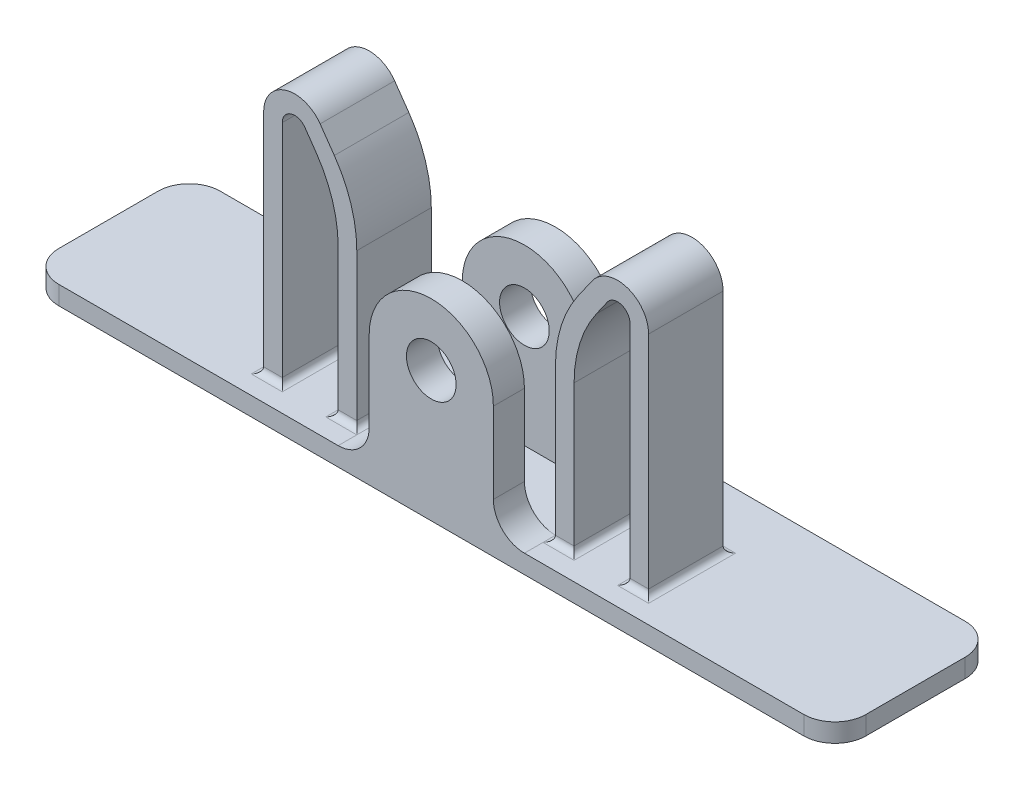
SolidWorks part; units mm, degrees
ref_plane "Front Plane" through (0, 0, 0) normal (0, 0, 1) x (1, 0, 0)
ref_plane "Top Plane" through (0, 0, 0) normal (0, 1, 0) x (1, 0, 0)
ref_plane "Right Plane" through (0, 0, 0) normal (1, 0, 0) x (0, 0, -1)
sketch "Sketch1" plane through (0, 0, 0) normal (0, 1, 0) x (1, 0, 0)
  line L1 (65, -10) -> (-65, -10)
  line L2 (65, -10) -> (65, 10)
  line L3 (65, 10) -> (-65, 10)
  line L4 (-65, -10) -> (-65, 10)
  line L5 (65, -10) -> (-65, 10) construction
  line L6 (65, 10) -> (-65, -10) construction
  point P0 (0, 0)
  dimension "D1" = 130
  dimension "D2" = 20
extrude "Boss-Extrude1" add sketch "Sketch1" along normal blind 3
sketch "Sketch2" plane through (0, 0, 10) normal (0, 0, 1) x (1, 0, 0)
  line L0 (-65, 3) -> (65, 3) construction
  line L2 (-10, 3) -> (10, 3)
  line L3 (-10, 3) -> (-10, 21)
  line L4 (-10, 21) -> (10, 21)
  line L5 (10, 3) -> (10, 21)
  circle A0 centre (0, 21) radius 10
  dimension "D1" = 20
  dimension "D2" = 18
extrude "Boss-Extrude2" add sketch "Sketch2" against normal blind 5 contours A0 | L3 L2 L5 L4
mirror "Mirror1" about plane through (0, 0, 0) normal (0, 0, 1) of "Boss-Extrude2"
sketch "Sketch6" plane through (0, 0, -10) normal (0, 0, -1) x (-1, 0, 0)
  line L1 (-65, 0) -> (65, 0)
  line L2 (-65, 0) -> (-65, 3)
  line L3 (-65, 3) -> (65, 3)
  line L4 (65, 0) -> (65, 3)
extrude "Boss-Extrude3" add sketch "Sketch6" along normal blind 6
sketch "Sketch7" plane through (0, 0, 0) normal (0, 0, 1) x (1, 0, 0)
  line L0 (16, 0) -> (16, 34)
  line L2 (16, 34) -> (21.9042, 42.4321)
  line L3 (31, 39.5642) -> (31, 0)
  line L4 (31, 0) -> (16, 0)
  line L6 (0, 0) -> (0, 33.9292) construction
  line L7 (16, 34) -> (31, 34) construction
  line L8 (-65, 0) -> (65, 0) construction
  arc A0 (21.9042, 42.4321) -> (31, 39.5642) centre (26, 39.5642) cw
  dimension "D6" = 5
  dimension "D1" = 55
  dimension "D2" = 15
  dimension "D4" = 16
  dimension "D5" = 34
extrude "Extrude-Thin1" add sketch "Sketch7" along normal mid plane 12 thin thin type one direction reverse wall 3
mirror "Mirror2" about plane through (0, 0, 0) normal (1, 0, 0) of "Extrude-Thin1"
fillet "Fillet1" radius 20 4 edges at (16, 34, 0) (-16, 34, 0) (19, 33.0541, 0) (-19, 33.0541, 0)
fillet "Fillet2" radius 5 4 edges at (-65, 1.5, -16) (65, 1.5, -16) (65, 1.5, 10) (-65, 1.5, 10)
fillet "Fillet3" radius 5 4 edges at (10, 3, -7.5) (-10, 3, -7.5) (-10, 3, 7.5) (10, 3, 7.5)
fillet "Fillet4" radius 1 16 edges at (-29.5, 3, 6) (-17.5, 3, 6) (-16, 3, 0) (-31, 3, 0) (-19, 3, 0) (-28, 3, 0) (-17.5, 3, -6) (-29.5, 3, -6) (29.5, 3, -6) (17.5, 3, -6) (19, 3, 0) (16, 3, 0) (17.5, 3, 6) (29.5, 3, 6) (28, 3, 0) (31, 3, 0)
sketch "Sketch8" plane through (0, 0, 10) normal (0, 0, 1) x (1, 0, 0)
  circle A0 centre (0, 21) radius 4
  dimension "D1" = 8
extrude "Cut-Extrude1" cut sketch "Sketch8" against normal up to surface (20 mm away) up to face at (0, 11.9882, -10)
